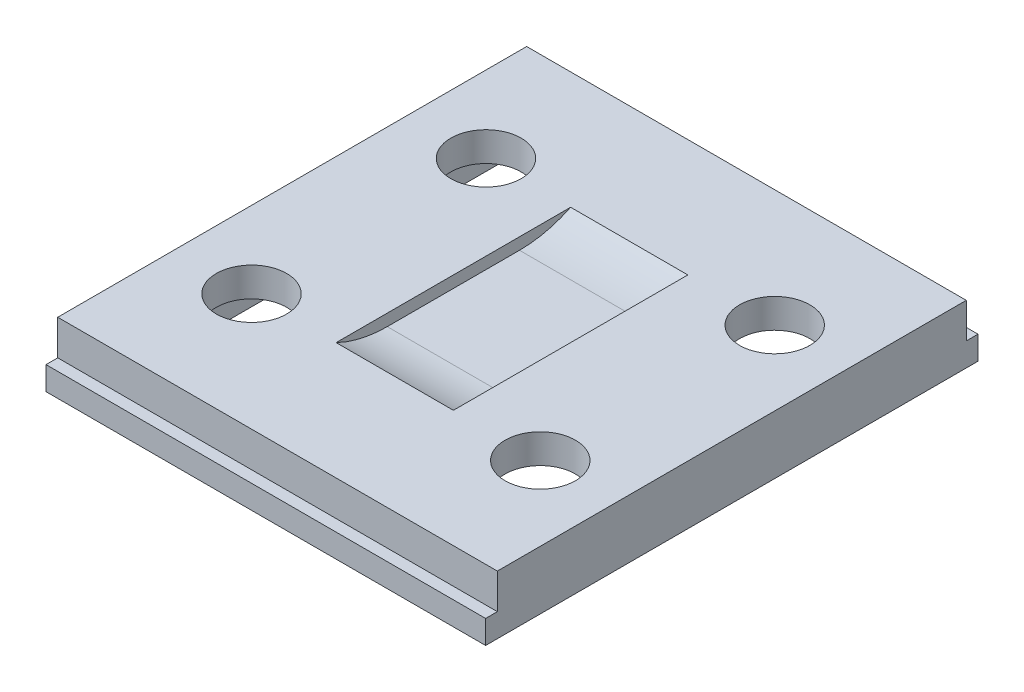
SolidWorks part; units mm, degrees
ref_plane "Front Plane" through (0, 0, 0) normal (0, 0, 1) x (1, 0, 0)
ref_plane "Top Plane" through (0, 0, 0) normal (0, 1, 0) x (1, 0, 0)
ref_plane "Right Plane" through (0, 0, 0) normal (1, 0, 0) x (0, 0, -1)
sketch "Sketch1" plane through (0, 0, 0) normal (0, 1, 0) x (1, 0, 0)
  line L1 (-18.75, -21) -> (18.75, -21)
  line L2 (-18.75, -21) -> (-18.75, 21)
  line L3 (-18.75, 21) -> (18.75, 21)
  line L4 (18.75, -21) -> (18.75, 21)
  line L5 (-18.75, -21) -> (18.75, 21) construction
  line L6 (-18.75, 21) -> (18.75, -21) construction
  point P0 (0, 0)
extrude "Boss-Extrude1" add sketch "Sketch1" along normal blind 5 contours L2 L3 L4 L1
sketch "Sketch2" plane through (0, 5, 0) normal (0, 1, 0) x (1, 0, 0)
  line L0 (18.75, -21) -> (18.75, 21) construction
  line L1 (-18.75, -21) -> (18.75, -21)
  line L2 (-18.75, -21) -> (-18.75, -20)
  line L3 (-18.75, -20) -> (18.75, -20)
  line L4 (18.75, -21) -> (18.75, -20)
extrude "Cut-Extrude1" cut sketch "Sketch2" against normal blind 3
sketch "Sketch3" plane through (0, 5, 0) normal (0, 1, 0) x (1, 0, 0)
  line L0 (18.75, -20) -> (18.75, 21) construction
  line L1 (-18.75, 21) -> (18.75, 21)
  line L2 (-18.75, 21) -> (-18.75, 20)
  line L3 (-18.75, 20) -> (18.75, 20)
  line L4 (18.75, 21) -> (18.75, 20)
extrude "Cut-Extrude2" cut sketch "Sketch3" against normal blind 3
sketch "Sketch4" plane through (0, 5, 0) normal (0, 1, 0) x (1, 0, 0)
  line L1 (-5, -10) -> (5, -10)
  line L2 (-5, -10) -> (-5, 10)
  line L3 (-5, 10) -> (5, 10)
  line L4 (5, -10) -> (5, 10)
  line L5 (-5, -10) -> (5, 10) construction
  line L6 (-5, 10) -> (5, -10) construction
  point P0 (0, 0)
extrude "Cut-Extrude3" cut sketch "Sketch4" against normal blind 1
fillet "Fillet1" radius 10 1 edges at (0, 4, -10)
fillet "Fillet2" radius 10 1 edges at (0, 4, 10)
shell "Shell1" thickness 2.5 removed face at (0, 0, 0)
sketch "Sketch5" plane through (0, 5, 0) normal (0, 1, 0) x (1, 0, 0)
  circle A0 centre (-12.22, -10) radius 3
  circle A1 centre (-12.22, 10) radius 3
  circle A2 centre (12.412, -10) radius 3
  circle A3 centre (12.412, 10) radius 3
extrude "Cut-Extrude4" cut sketch "Sketch5" against normal blind 2.5
